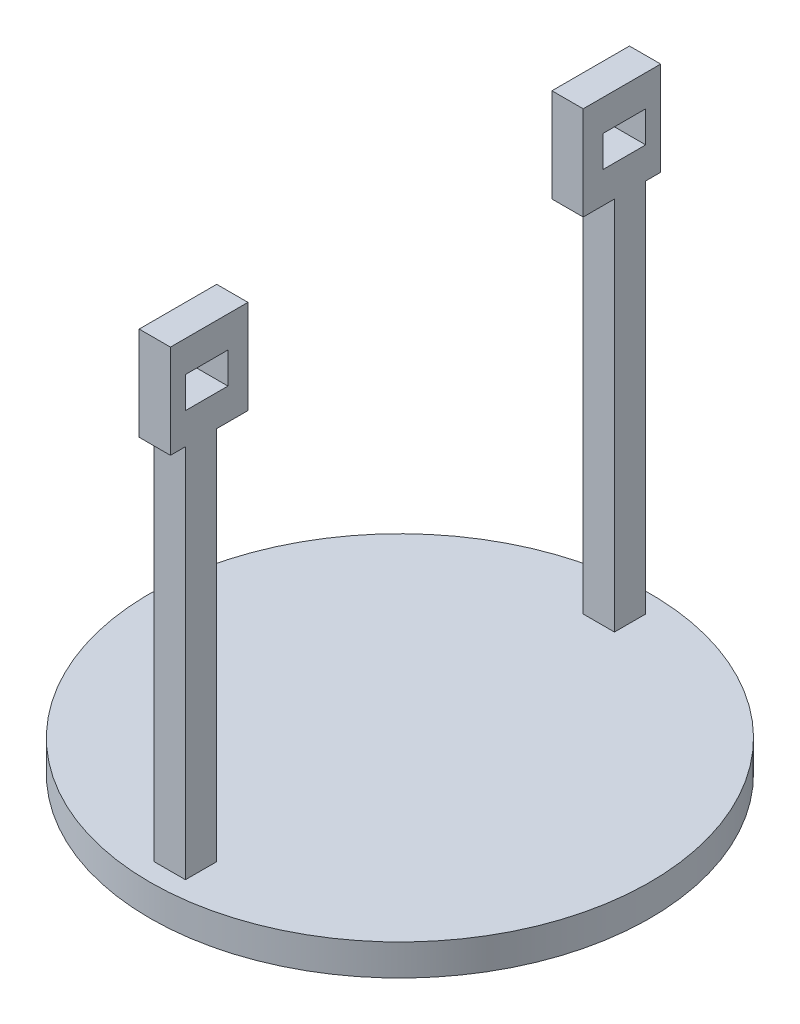
SolidWorks part; units mm, degrees
ref_plane "Front Plane" through (0, 0, 0) normal (0, 0, 1) x (1, 0, 0)
ref_plane "Top Plane" through (0, 0, 0) normal (0, 1, 0) x (1, 0, 0)
ref_plane "Right Plane" through (0, 0, 0) normal (1, 0, 0) x (0, 0, -1)
sketch "Sketch1" plane through (0, 0, 0) normal (0, 1, 0) x (1, 0, 0)
  circle A0 centre (0, 0) radius 50.8
extrude "Boss-Extrude1" add sketch "Sketch1" along normal blind 6.35
ref_plane "Plane6" through (0, 0, 0) normal (1, 0, 0) x (0, 0, -1)
ref_axis "Axis1" through (0, 44.0758, 0) along (0, -1, 0)
sketch "Sketch9" plane through (0, 0, 0) normal (1, 0, 0) x (0, 0, -1)
  line L0 (0, 6.35) -> (40.4084, 6.35)
  line L1 (50.8, 6.35) -> (-50.8, 6.35) construction
  line L2 (50.8, 0) -> (50.8, 6.35) construction
  line L3 (40.4084, 6.35) -> (46.7584, 6.35)
  line L4 (40.4084, 6.35) -> (40.4084, 82.55)
  line L5 (40.4084, 82.55) -> (46.7584, 82.55)
  line L6 (46.7584, 6.35) -> (46.7584, 82.55)
  line L7 (46.7584, 82.55) -> (49.8064, 82.55)
  line L8 (46.7584, 82.55) -> (46.7584, 88.9)
  line L9 (49.8064, 82.55) -> (34.0584, 82.55)
  line L10 (49.8064, 82.55) -> (49.8064, 101.6)
  line L11 (49.8064, 101.6) -> (34.0584, 101.6)
  line L12 (34.0584, 82.55) -> (34.0584, 101.6)
  line L14 (46.7584, 88.9) -> (38.1224, 88.9)
  line L15 (46.7584, 88.9) -> (46.7584, 95.25)
  line L16 (46.7584, 95.25) -> (38.1224, 95.25)
  line L17 (38.1224, 88.9) -> (38.1224, 95.25)
  dimension "D1" = 6.35
  dimension "D2" = 76.2
  dimension "D3" = 4.0416
  dimension "D4" = 6.35
  dimension "D5" = 6.35
  dimension "D6" = 6.35
  dimension "D7" = 4.064
  dimension "D8" = 3.048
  dimension "D9" = 6.35
  dimension "D10" = 40.4084
extrude "Boss-Extrude5" add sketch "Sketch9" along normal mid plane 6.35 contours L3 L6 L5 L4 | L14 L17 L16 L15 L7 L10 L11 L12 L9 L5 region at (0, 44.45, -43.5834) region at (0, 82.7972, -37.2334)
mirror "Mirror1" about plane through (0, 0, 0) normal (0, 0, 1) of "Boss-Extrude5"
